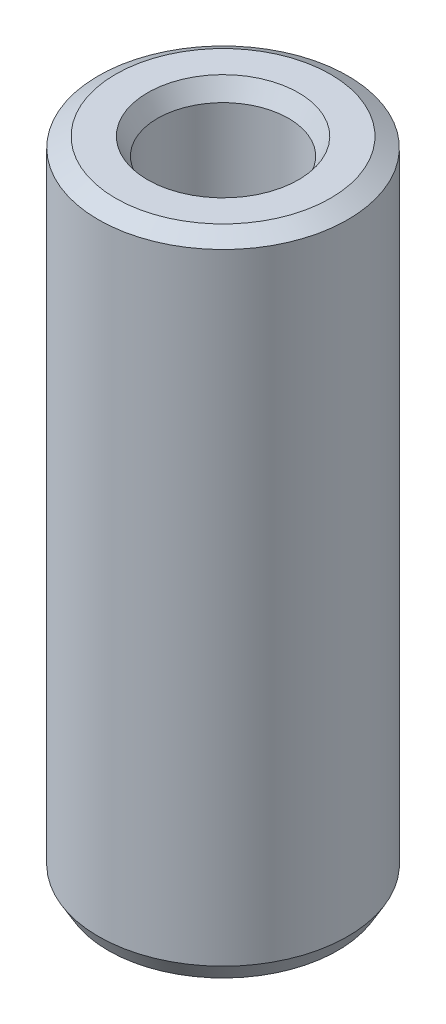
SolidWorks part; units mm, degrees
ref_plane "Front Plane" through (0, 0, 0) normal (0, 0, 1) x (1, 0, 0)
ref_plane "Top Plane" through (0, 0, 0) normal (0, 1, 0) x (1, 0, 0)
ref_plane "Right Plane" through (0, 0, 0) normal (1, 0, 0) x (0, 0, -1)
sketch "Sketch1" plane through (0, 0, 0) normal (0, 1, 0) x (1, 0, 0)
  circle A0 centre (0, 0) radius 27.5
  dimension "SLEEVE_OD" = 55
extrude "Boss-Extrude1" add sketch "Sketch1" along normal blind 142.8916
sketch "Sketch2" plane through (0, 0, 0) normal (0, 1, 0) x (1, 0, 0)
  circle A0 centre (0, 0) radius 14.4533
  dimension "BORE_D" = 28.9065
extrude "Cut-Extrude1" cut sketch "Sketch2" along normal through all
chamfer "Chamfer1" distance 2.1942 angle 60 4 edges at (0, 142.8916, 14.4533) (0, 0, 14.4533) (0, 0, 27.5) (0, 142.8916, 27.5) first distance on face at (0, 142.8916, 14.4533) first distance on face at (0, 0, 14.4533) first distance on face at (0, 142.8916, 27.5)
